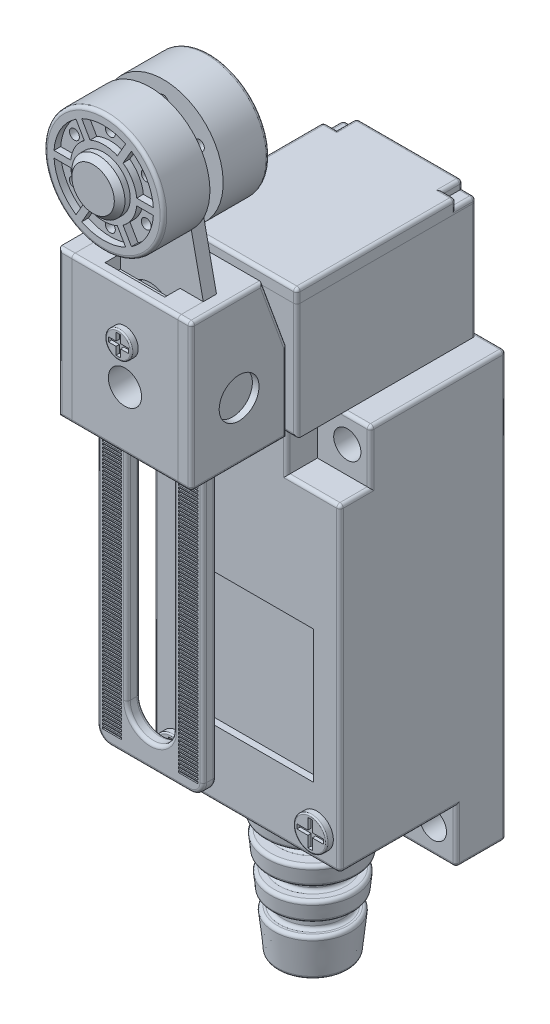
SolidWorks part; units mm, degrees
ref_plane "前视基准面" through (0, 0, 0) normal (0, 0, 1) x (1, 0, 0)
ref_plane "上视基准面" through (0, 0, 0) normal (0, 1, 0) x (1, 0, 0)
ref_plane "右视基准面" through (0, 0, 0) normal (1, 0, 0) x (0, 0, -1)
sketch "草图1" plane through (0, 0, 0) normal (0, 0, 1) x (1, 0, 0)
  line L0 (-30.7648, 0) -> (29.1625, 0) construction
  line L1 (0, 42.5) -> (0, 12.5) construction
  line L2 (-10, 24) -> (10, 24) construction
  line L3 (10, 24) -> (10, 4.5) construction
  line L4 (10, 4.5) -> (14, 4.5)
  line L5 (14, 4.5) -> (14, -59.5)
  line L6 (14, -59.5) -> (-14, -59.5)
  line L7 (-14, -59.5) -> (-14, 4.5)
  line L8 (-14, 4.5) -> (-10, 4.5)
  line L9 (-10, 4.5) -> (-10, 24) construction
  line L10 (-10, 4.5) -> (10, 4.5)
  line L11 (0, 0) -> (0, -73.5) construction
  line L12 (0, 0) -> (0, 12.5) construction
  line L13 (25, 42.5) -> (25, 12.5) construction
  line L14 (25, 12.5) -> (25, -37.5) construction
  line L15 (25, 42.5) -> (25, 48.5) construction
  arc A0 (11.2553, 40.3086) -> (-10.9644, 40.4246) centre (0, 12.5) ccw construction
  dimension "L" = 30
  dimension "D1" = 80
  dimension "A" = 28
  dimension "D2" = 6
  dimension "B2" = 64
  dimension "D3" = 20
  dimension "D4" = 25
  dimension "C" = 19.5
  dimension "B" = 12.5
  dimension "D6" = 4.5
  dimension "B1" = 14
extrude "凸台-拉伸1" add sketch "草图1" along normal mid plane 25
sketch "草图2" plane through (14, 0, 0) normal (1, 0, 0) x (0, 0, -1)
  line L0 (-12.5, -59.5) -> (-12.5, -51.5)
  line L1 (-12.5, -59.5) -> (5, -59.5)
  line L2 (-12.5, -51.5) -> (5, -51.5)
  line L3 (5, -59.5) -> (5, -51.5)
  line L4 (-12.5, -59.5) -> (-12.5, 4.5) construction
  line L5 (12.5, -59.5) -> (12.5, 4.5) construction
  dimension "F" = 7.5
  dimension "D2" = 8
extrude "切除-拉伸1" cut sketch "草图2" against normal through all
sketch "草图3" plane through (14, 0, 0) normal (1, 0, 0) x (0, 0, -1)
  line L0 (-12.5, 4.5) -> (-7.9, 4.5)
  line L1 (-12.5, 4.5) -> (-12.5, -3.5)
  line L2 (-7.9, 4.5) -> (-7.9, -3.5)
  line L3 (-12.5, -3.5) -> (-7.9, -3.5)
  line L4 (-12.5, 4.5) -> (12.5, 4.5) construction
  line L5 (12.5, -59.5) -> (12.5, 4.5) construction
  dimension "G" = 20.4
  dimension "D2" = 8
extrude "切除-拉伸2" cut sketch "草图3" against normal blind 8
mirror "镜向1" about plane through (0, 0, 0) normal (1, 0, 0) of "切除-拉伸2"
sketch "草图4" plane through (0, 0, 7.9) normal (0, 0, 1) x (1, 0, 0)
  line L0 (-10.5, 0.5314) -> (-10.5, -55.4686) construction
  line L2 (-6, 4.5) -> (-14, 4.5) construction
  line L3 (0, 0) -> (0, -19.4871) construction
  circle A0 centre (-10.5, 0.5314) radius 2.05
  circle A1 centre (-10.5, -55.4686) radius 2.05
  point P6 (-10, 4.5)
  dimension "D1" = 4.1
  dimension "I" = 4.1
  dimension "D4" = 4
  dimension "H" = 56
  dimension "A1" = 21
extrude "切除-拉伸3" cut sketch "草图4" against normal through all
mirror "镜向2" about plane through (0, 0, 0) normal (1, 0, 0) of "切除-拉伸3"
sketch "草图5" plane through (0, -51.5, 0) normal (0, -1, 0) x (1, 0, 0)
  line L0 (-14, -12.5) -> (14, -12.5) construction
  line L1 (0, -2.067) -> (0, 4.1058) construction
  circle A0 centre (0, 2.6) radius 7.55
  dimension "D1" = 15.1
  dimension "D2" = 15.1
extrude "凸台-拉伸3" add sketch "草图5" along normal up to vertex (22 mm away) draft 6 up to point (0, -73.5, 0)
ref_plane "基准面1" through (0, 0, 2.6) normal (0, 0, -1) x (-1, 0, 0)
sketch "草图6" plane through (0, 0, 2.6) normal (0, 0, -1) x (-1, 0, 0)
  line L0 (0, -51.5) -> (0, -73.5) construction
  line L1 (-7.55, -51.5) -> (7.55, -51.5) construction
  line L2 (-5.2377, -73.5) -> (5.2377, -73.5) construction
  line L3 (-4.5, -55.5) -> (-7.5, -55.5)
  line L4 (-4.5, -55.5) -> (-4.5, -57.5)
  line L5 (-7.5, -55.5) -> (-7.5, -57.5)
  line L6 (-4.5, -57.5) -> (-7.5, -57.5)
  line L9 (-4.5, -60.5) -> (-7.5, -60.5)
  line L10 (-4.5, -60.5) -> (-4.5, -62.5)
  line L11 (-7.5, -60.5) -> (-7.5, -62.5)
  line L13 (-4.5, -62.5) -> (-7.5, -62.5)
  line L15 (-4.5, -65.5) -> (-6.5, -65.5)
  line L16 (-4.5, -65.5) -> (-4.5, -67.5)
  line L18 (-6.5, -65.5) -> (-6.5, -67.5)
  line L19 (-4.5, -67.5) -> (-6.5, -67.5)
  line L21 (-4.5, -55.5) -> (-4.5, -51.5) construction
  line L22 (-4.5, -60.5) -> (-4.5, -57.5) construction
  line L23 (-4.5, -65.5) -> (-4.5, -62.5) construction
  dimension "D1" = 4
  dimension "D2" = 2
  dimension "D3" = 3
  dimension "D4" = 3
  dimension "D5" = 4.5
  dimension "D6" = 2
  dimension "D7" = 2
  dimension "D8" = 3
  dimension "D9" = 3
  dimension "D10" = 2
revolve "切除-旋转1" cut sketch "草图6" angle 360 about L0
sketch "草图7" plane through (0, 0, 12.5) normal (0, 0, 1) x (1, 0, 0)
  line L0 (0, 0) -> (0, -48.4796) construction
  line L1 (-14, -51.5) -> (14, -51.5) construction
  line L2 (6, 4.5) -> (-6, 4.5) construction
  circle A0 centre (-10.5, -47.5) radius 2.5
  circle A1 centre (10.5, -47.5) radius 2.5
  circle A2 centre (0, 0.5) radius 2.5
  dimension "M3" = 5
  dimension "D2" = 21
  dimension "D3" = 4
  dimension "D4" = 4
extrude "凸台-拉伸4" add sketch "草图7" along normal blind 1
sketch "草图8" plane through (0, 0, 13.5) normal (0, 0, 1) x (1, 0, 0)
  line L0 (-14, -47.5) -> (-7.3529, -47.5) construction
  line L1 (-14, -3.5) -> (-14, -51.5) construction
  line L2 (-10.5, -50.6113) -> (-10.5, -43.7188) construction
  line L3 (7.0475, -47.5) -> (13.5803, -47.5) construction
  line L4 (10.5, -50.6113) -> (10.5, -43.7188) construction
  line L5 (-3.5148, 0.5) -> (3.3232, 0.5) construction
  line L6 (0, -2.9168) -> (0, 3.9916) construction
  line L7 (-2, 0.84) -> (-2, 0.16)
  line L8 (-2, 0.84) -> (-0.325, 0.84)
  line L9 (-2, 0.16) -> (-0.325, 0.16)
  line L10 (2, 0.84) -> (2, 0.16)
  line L11 (-0.325, -1.5) -> (0.325, -1.5)
  line L12 (-0.325, -1.5) -> (-0.325, 0.16)
  line L13 (0.325, -1.5) -> (0.325, 0.16)
  line L14 (-0.325, 2.5) -> (0.325, 2.5)
  line L15 (-12.5, -47.16) -> (-12.5, -47.84)
  line L16 (-12.5, -47.16) -> (-10.84, -47.16)
  line L17 (-12.5, -47.84) -> (-10.84, -47.84)
  line L18 (-8.5, -47.16) -> (-8.5, -47.84)
  line L19 (-10.84, -49.5) -> (-10.16, -49.5)
  line L20 (-10.84, -49.5) -> (-10.84, -47.84)
  line L21 (-10.16, -49.5) -> (-10.16, -47.84)
  line L22 (-10.84, -45.5) -> (-10.16, -45.5)
  line L23 (-10.16, -47.16) -> (-8.5, -47.16)
  line L24 (-10.84, -47.16) -> (-10.84, -45.5)
  line L25 (-10.16, -47.16) -> (-10.16, -45.5)
  line L26 (-10.16, -47.84) -> (-8.5, -47.84)
  line L27 (0.325, 0.84) -> (2, 0.84)
  line L28 (-0.325, 0.84) -> (-0.325, 2.5)
  line L29 (0.325, 0.16) -> (2, 0.16)
  line L30 (0.325, 0.84) -> (0.325, 2.5)
  line L31 (10.84, -47.84) -> (12.5, -47.84)
  line L32 (8.5, -47.16) -> (10.16, -47.16)
  line L33 (8.5, -47.16) -> (8.5, -47.84)
  line L34 (8.5, -47.84) -> (10.16, -47.84)
  line L35 (12.5, -47.16) -> (12.5, -47.84)
  line L36 (10.16, -45.5) -> (10.84, -45.5)
  line L37 (10.16, -45.5) -> (10.16, -47.16)
  line L38 (10.16, -49.5) -> (10.84, -49.5)
  line L39 (10.84, -45.5) -> (10.84, -47.16)
  line L40 (10.16, -47.84) -> (10.16, -49.5)
  line L41 (10.84, -47.16) -> (12.5, -47.16)
  line L42 (10.84, -47.84) -> (10.84, -49.5)
  dimension "D1" = 0.68
  dimension "D2" = 0.65
  dimension "D3" = 4
  dimension "D4" = 4
  dimension "D5" = 0.68
  dimension "D6" = 0.68
  dimension "D7" = 4
  dimension "D8" = 4
  dimension "D9" = 0.68
  dimension "D10" = 0.68
  dimension "D11" = 4
  dimension "D12" = 4
extrude "切除-拉伸4" cut sketch "草图8" against normal blind 0.5
fillet "圆角1" radius 0.5 29 edges at (0, 4.5, -12.5) (14, 4.5, -2.3) (10, 4.5, 7.9) (14, 0.5, 7.9) (14, -3.5, 10.2) (10, -3.5, 12.5) (6, 0.5, 12.5) (6, 4.5, 10.2) (-6, 4.5, 10.2) (0, 4.5, 12.5) (-14, 4.5, -2.3) (-10, 4.5, 7.9) (-14, 0.5, 7.9) (-6, 0.5, 12.5) (-10, -3.5, 12.5) (-14, -27.5, -12.5) (-14, -27.5, 12.5) (-14, -51.5, 3.75) (-14, -59.5, -8.75) (-14, -55.5, -5) (0, -59.5, -12.5) (0, -59.5, -5) (14, -27.5, -12.5) (14, -59.5, -8.75) (14, -55.5, -5) (14, -51.5, 3.75) (0, -51.5, 12.5) (14, -27.5, 12.5) (-14, -3.5, 10.2)
fillet "圆角3" radius 0.5 13 edges at (-7.1296, -55.5, 2.6) (6.9194, -57.5, 2.6) (-4.5, -55.5, 2.6) (-4.5, -57.5, 2.6) (-6.6041, -60.5, 2.6) (-4.5, -60.5, 2.6) (6.3939, -62.5, 2.6) (-4.5, -62.5, 2.6) (-6.0785, -65.5, 2.6) (-4.5, -65.5, 2.6) (-4.5, -67.5, 2.6) (5.8683, -67.5, 2.6) (5.2377, -73.5, 2.6)
sketch "草图9" plane through (0, 0, 12.5) normal (0, 0, 1) x (1, 0, 0)
  line L0 (-14, -51) -> (-14, -4) construction
  line L1 (-10, -21.5) -> (10, -21.5)
  line L2 (-10, -21.5) -> (-10, -41.5)
  line L3 (-10, -41.5) -> (10, -41.5)
  line L4 (10, -21.5) -> (10, -41.5)
  line L5 (-7.55, -51.5) -> (7.55, -51.5) construction
  dimension "D1" = 20
  dimension "D2" = 4
  dimension "D3" = 20
  dimension "D4" = 10
extrude "切除-拉伸5" cut sketch "草图9" against normal blind 1
sketch "草图10" plane through (0, 0, 0) normal (1, 0, 0) x (0, 0, -1)
  line L0 (12, 14.25) -> (-34.4, 14.25) construction
  line L1 (12, 4.5) -> (-15, 4.5)
  line L2 (12, 4.5) -> (12, 24)
  line L3 (12, 24) -> (-15, 24)
  line L4 (-15, 4.5) -> (-15, 24)
  line L5 (-16.5, 5.5) -> (-30.9, 5.5)
  line L6 (-30.9, 5.5) -> (-30.9, 27.5)
  line L7 (-30.9, 27.5) -> (-20.1397, 27.5)
  line L8 (12, 54) -> (-35.7, 54) construction
  line L9 (-20.1397, 27.5) -> (-16.5, 17.5)
  line L10 (12, 24) -> (12, 54) construction
  line L11 (-16.5, 17.5) -> (-16.5, 5.5)
  line L12 (12, 50) -> (-21.5, 50) construction
  line L13 (12, 48) -> (-30.7, 48) construction
  line L14 (12, 52) -> (-16.5, 52) construction
  line L16 (2, 4.5) -> (2, 7.4237) construction
  line L17 (12.5, 4) -> (12.5, -59) construction
  dimension "D12" = 2
  dimension "J" = 19.5
  dimension "D2" = 27
  dimension "D3" = 3.5
  dimension "K" = 46.4
  dimension "D4" = 1
  dimension "D5" = 1.5
  dimension "D6" = 22
  dimension "D7" = 10
  dimension "D8" = 20
  dimension "D11" = 2
  dimension "D17" = 2
  dimension "C3" = 47.7
  dimension "D18" = 30
  dimension "N" = 28.5
  dimension "O" = 10.5
  dimension "C2" = 33.5
  dimension "C1" = 42.7
extrude "凸台-拉伸5" add sketch "草图10" along normal mid plane 20
sketch "草图11" plane through (0, 0, 30.9) normal (0, 0, 1) x (1, 0, 0)
  circle A0 centre (0, 14.25) radius 3
  dimension "D1" = 6
extrude "凸台-拉伸6" add sketch "草图11" against normal up to surface (15.9 mm away) up to face at (0, 14.25, 15)
sketch "草图12" plane through (0, 5.5, 0) normal (0, -1, 0) x (1, 0, 0)
  line L0 (0, 30.9) -> (0, 19.6877) construction
  line L1 (-8, 27.1) -> (8, 27.1)
  line L2 (-8, 27.1) -> (-8, 25.1)
  line L3 (-8, 25.1) -> (8, 25.1)
  line L4 (8, 27.1) -> (8, 25.1)
  line L5 (10, 30.9) -> (-10, 30.9) construction
  line L6 (0, -12) -> (0, 21.5) construction
  dimension "D1" = 2
  dimension "D2" = 3.8
  dimension "D3" = 16
extrude "凸台-拉伸7" add sketch "草图12" along normal up to vertex (-43 mm away) and the other way up to vertex (-43 mm away) up to point (25, 48.5, 0) other way up to point (25, -37.5, 0)
sketch "草图13" plane through (0, 0, 27.1) normal (0, 0, 1) x (1, 0, 0)
  line L0 (0, -33.4812) -> (0, 45.9522) construction
  line L1 (0, 22.5) -> (0, -30.5) construction
  line L2 (3.5, 22.5) -> (3.5, -30.5)
  line L3 (-3.5, 22.5) -> (-3.5, -30.5)
  line L4 (8, -37.5) -> (-8, -37.5) construction
  line L5 (-8, 27.5) -> (-4.5283, 43.8331)
  line L6 (8, 27.5) -> (4.5283, 43.8331)
  line L7 (-8, 27.5) -> (-8, 48.5)
  line L8 (-8, 48.5) -> (8, 48.5)
  line L9 (8, 48.5) -> (8, 27.5)
  line L10 (8, 27.5) -> (-8, 27.5) construction
  line L11 (0, 47.5) -> (2.6556, 47.5) construction
  arc A0 (3.5, 22.5) -> (-3.5, 22.5) centre (0, 22.5) ccw
  arc A1 (-3.5, -30.5) -> (3.5, -30.5) centre (0, -30.5) ccw
  arc A2 (-4.5283, 43.8331) -> (4.5283, 43.8331) centre (0, 42.8705) cw
  point P5 (0, -4)
  dimension "D4" = 1
  dimension "D1" = 7
  dimension "D2" = 7
  dimension "D3" = 53
  dimension "D5" = 78
extrude "切除-拉伸6" cut sketch "草图13" against normal up to surface (2 mm away) up to face at (0, 38, 25.1)
sketch "草图14" plane through (0, 5.5, 0) normal (0, -1, 0) x (1, 0, 0)
  line L0 (-8, 27.1) -> (-8, 30.9)
  line L1 (10, 30.9) -> (-10, 30.9) construction
  line L2 (8, 27.1) -> (8, 30.9)
split line "分割线1"
sketch "草图15" plane through (0, 0, 30.9) normal (0, 0, 1) x (1, 0, 0)
  line L0 (-8, 5.5) -> (-8, 27.5)
  line L1 (8, 27.5) -> (8, 5.5)
split line "分割线2"
sketch "草图16" plane through (0, 5.5, 0) normal (0, -1, 0) x (1, 0, 0)
  line L0 (8, 27.1) -> (8, 30.9) construction
  line L1 (-4.5, 29.4) -> (4.5, 29.4)
  line L2 (-4.5, 29.4) -> (-4.5, 27.1)
  line L3 (-4.5, 27.1) -> (4.5, 27.1)
  line L4 (4.5, 29.4) -> (4.5, 27.1)
  line L5 (-8, 27.1) -> (-8, 30.9) construction
  line L6 (8, 30.9) -> (-8, 30.9) construction
  line L7 (8, 27.1) -> (-8, 27.1) construction
  dimension "D1" = 3.5
  dimension "D2" = 3.5
  dimension "D3" = 1.5
extrude "切除-拉伸7" cut sketch "草图16" against normal blind 2
ref_plane "基准面2" through (0, 16.5, 0) normal (0, 1, 0) x (-1, 0, 0)
sketch "草图17" plane through (0, 0, 27.1) normal (0, 0, 1) x (1, 0, 0)
  circle A0 centre (0, 42.5) radius 9
  dimension "P" = 18
extrude "凸台-拉伸8" add sketch "草图17" along normal blind 7
mirror "镜向4" about plane through (0, 16.5, 0) normal (0, 1, 0) of "切除-拉伸7"
sketch "草图18" plane through (0, 0, 34.1) normal (0, 0, 1) x (1, 0, 0)
  circle A0 centre (0, 42.5) radius 7.5
  circle A1 centre (0, 42.5) radius 5
  dimension "D1" = 15
  dimension "D2" = 10
extrude "切除-拉伸8" cut sketch "草图18" against normal blind 1
sketch "草图19" plane through (0, 0, 33.1) normal (0, 0, 1) x (1, 0, 0)
  line L0 (0, 47.5) -> (0, 50) construction
  circle A0 centre (0, 42.5) radius 5 construction
  circle A1 centre (0, 42.5) radius 5 construction
  circle A2 centre (0, 42.5) radius 7.5 construction
  circle A3 centre (0, 48.75) radius 0.75
  dimension "D1" = 1.5
extrude "切除-拉伸11" cut sketch "草图19" against normal up to surface (6 mm away) up to face at (0, 44.702, 27.1)
sketch "草图20" plane through (0, 0, 33.1) normal (0, 0, 1) x (1, 0, 0)
  line L0 (-10.0844, 42.5) -> (9.682, 42.5) construction
  line L1 (0, 42.5) -> (0, 12.5) construction
  line L2 (4.5, 43) -> (8, 43)
  line L3 (4.5, 43) -> (4.5, 42)
  line L4 (4.5, 42) -> (8, 42)
  line L5 (8, 43) -> (8, 42)
  dimension "D1" = 1
  dimension "D2" = 4.5
  dimension "D3" = 3.5
extrude "凸台-拉伸9" add sketch "草图20" along normal blind 1
pattern_circular "阵列(圆周)1" count 6 every 60 about axis through (0, 42.5, 34.1) along (0, 0, 1) of "凸台-拉伸9", "切除-拉伸11"
ref_plane "基准面3" through (0, 0, 26.1) normal (0, 0, -1) x (-1, 0, 0)
mirror "镜向6" about plane through (0, 0, 26.1) normal (0, 0, -1) of "切除-拉伸8", "凸台-拉伸8"
sketch "草图26" plane through (0, 0, 19.1) normal (0, 0, -1) x (-1, 0, 0)
  line L0 (0, 47.5) -> (0, 50) construction
  circle A0 centre (0, 42.5) radius 5 construction
  circle A1 centre (0, 42.5) radius 5 construction
  circle A2 centre (0, 42.5) radius 7.5 construction
  circle A3 centre (0, 48.75) radius 0.75
  dimension "D1" = 1.5
extrude "切除-拉伸15" cut sketch "草图26" against normal up to surface (6 mm away) up to face at (0, 44.702, 25.1)
sketch "草图27" plane through (0, 0, 19.1) normal (0, 0, -1) x (-1, 0, 0)
  line L0 (-9.6322, 42.5) -> (9.676, 42.5) construction
  line L2 (4.5, 43) -> (8, 43)
  line L3 (4.5, 43) -> (4.5, 42)
  line L4 (4.5, 42) -> (8, 42)
  line L5 (8, 43) -> (8, 42)
  circle A0 centre (0, 42.5) radius 5 construction
  dimension "D1" = 1
  dimension "D2" = 3.5
  dimension "D3" = 4.5
extrude "凸台-拉伸12" add sketch "草图27" along normal up to surface (1 mm away) up to face at (9, 42.5, 18.1)
pattern_circular "阵列(圆周)3" count 6 every 60 about axis through (0, 42.5, 18.1) along (0, 0, 1) of "凸台-拉伸12", "切除-拉伸15"
sketch "草图21" plane through (0, 0, 34.1) normal (0, 0, 1) x (1, 0, 0)
  circle A0 centre (0, 42.5) radius 4
  dimension "D1" = 8
extrude "凸台-拉伸10" add sketch "草图21" along normal up to vertex (1.6 mm away) and the other way up to vertex (17.6 mm away) up to point (0, 54, 35.7) other way up to point (0, 52, 16.5)
sketch "草图22" plane through (0, 0, 30.9) normal (0, 0, 1) x (1, 0, 0)
  circle A0 centre (0, 14.25) radius 2.5
  dimension "D1" = 5
extrude "切除-拉伸12" cut sketch "草图22" against normal up to surface (3.8 mm away) up to face at (0, -7.2917, 27.1)
sketch "草图23" plane through (0, 0, 30.9) normal (0, 0, 1) x (1, 0, 0)
  line L0 (0, 27.5) -> (0, 17.5) construction
  circle A0 centre (0, 20.25) radius 2
  circle A1 centre (0, 14.25) radius 2.5 construction
  dimension "M4" = 4
  dimension "D2" = 6
extrude "凸台-拉伸11" add sketch "草图23" along normal blind 1
sketch "草图24" plane through (0, 0, 31.9) normal (0, 0, 1) x (1, 0, 0)
  line L0 (-2.8059, 20.25) -> (2.5571, 20.25) construction
  line L1 (0, 17.5) -> (0, 23.3979) construction
  line L2 (0, 27.5) -> (0, 17.5) construction
  line L3 (0, 17.5) -> (0, 5.5) construction
  line L4 (0.34, 20.59) -> (1.5, 20.59)
  line L5 (-1.5, 20.59) -> (-0.34, 20.59)
  line L6 (-1.5, 20.59) -> (-1.5, 19.91)
  line L7 (-1.5, 19.91) -> (-0.34, 19.91)
  line L8 (1.5, 20.59) -> (1.5, 19.91)
  line L9 (-0.34, 21.75) -> (0.34, 21.75)
  line L10 (-0.34, 21.75) -> (-0.34, 20.59)
  line L11 (-0.34, 18.75) -> (0.34, 18.75)
  line L12 (0.34, 21.75) -> (0.34, 20.59)
  line L13 (-0.34, 19.91) -> (-0.34, 18.75)
  line L14 (0.34, 19.91) -> (1.5, 19.91)
  line L15 (0.34, 19.91) -> (0.34, 18.75)
  dimension "D1" = 0.68
  dimension "D2" = 0.68
  dimension "D3" = 3
  dimension "D4" = 3
extrude "切除-拉伸13" cut sketch "草图24" against normal blind 0.5
sketch "草图25" plane through (10, 0, 0) normal (1, 0, 0) x (0, 0, -1)
  line L0 (-23.7, 14.25) -> (-15, 14.25) construction
  line L1 (-15, 17.25) -> (-15, 11.25) construction
  line L2 (-23.7, 5.5) -> (-23.7, 18.9404) construction
  line L3 (-30.9, 5.5) -> (-16.5, 5.5) construction
  circle A0 centre (-23.7, 14.25) radius 3
  dimension "M6" = 6
extrude "切除-拉伸14" cut sketch "草图25" against normal blind 1
cosmetic thread "装饰螺纹线1" parameters "D2"=6
sketch "草图28" plane through (10, 0, 0) normal (1, 0, 0) x (0, 0, -1)
  line L0 (-15, 22) -> (12, 22)
  line L1 (-15, 24) -> (-15, 4.5) construction
  line L2 (12, 4.5) -> (12, 24) construction
  line L3 (12, 24) -> (-15, 24) construction
  dimension "D1" = 2
split line "分割线3"
sketch "草图29" plane through (0, 0, -12) normal (0, 0, -1) x (-1, 0, 0)
  line L0 (-10, 22) -> (10, 22)
split line "分割线4"
sketch "草图30" plane through (10, 0, 0) normal (1, 0, 0) x (0, 0, -1)
  line L1 (12, 24) -> (9, 24)
  line L2 (12, 24) -> (12, 22.75)
  line L3 (12, 22.75) -> (9, 22.75)
  line L4 (9, 24) -> (9, 22.75)
  dimension "D1" = 1.25
  dimension "D2" = 3
extrude "切除-拉伸16" cut sketch "草图30" against normal blind 2
mirror "镜向7" about plane through (0, 0, 0) normal (1, 0, 0) of "切除-拉伸16"
fillet "圆角5" radius 0.5 58 edges at (-3.5, -12.5, 25.1) (0, -34, 25.1) (0, -34, 27.1) (9, 5.5, 30.9) (9, 27.5, 30.9) (-9, 27.5, 30.9) (0, 27.5, 30.9) (-10, 22.5, 18.3199) (-10, 11.5, 16.5) (8, -16, 25.1) (3.5, -12.5, 25.1) (0, -37.5, 25.1) (0, -37.5, 27.1) (3.5, -11.5, 27.1) (-3.5, -11.5, 27.1) (-8, -16, 25.1) (-8, -16, 27.1) (4.5, 5.5, 28.25) (-4.5, 5.5, 28.25) (0, 5.5, 29.4) (4.5, 6.5, 29.4) (-4.5, 6.5, 29.4) (-10, 16.5, 30.9) (0, 5.5, 30.9) (-9, 5.5, 30.9) (10, 16.5, 30.9) (10, 27.5, 25.5199) (10, 22.5, 18.3199) (10, 11.5, 16.5) (10, 5.5, 23.7) (0, 4.5, 15) (-10, 23, 15) (-10, 13.25, 15) (-10, 24, 3) (-8, 24, -10.5) (-9, 24, -9) (-10, 23.375, -9) (-10, 22.75, -10.5) (-9, 22.75, -12) (-8, 23.375, -12) (-10, 13.25, -12) (-10, 22.375, -12) (0, 24, -12) (9, 22.75, -12) (8, 23.375, -12) (8, 24, -10.5) (9, 24, -9) (10, 23.375, -9) (10, 22.75, -10.5) (10, 22.375, -12) (10, 13.25, -12) (10, 24, 3) (10, 23, 15) (10, 13.25, 15) (8, -16, 27.1) (9, 42.5, 18.1) (9, 42.5, 34.1) (0, 24, 15)
fillet "圆角6" radius 2 6 edges at (7.8536, -37.3536, 26.9536) (7.8536, -37.3536, 25.2464) (-7.8536, -37.3536, 25.2464) (-7.8536, -37.3536, 26.9536) (-8, -37.5, 26.1) (8, -37.5, 26.1)
fillet "圆角7" radius 0.2 4 edges at (-8, -47.5, 13.5) (13, -47.5, 13.5) (2.5, 0.5, 13.5) (2, 20.25, 31.9)
chamfer "倒角1" distance 0.8 angle 45 2 edges at (4, 42.5, 16.5) (4, 42.5, 35.7)
sketch "草图31" plane through (0, 0, 27.1) normal (0, 0, 1) x (1, 0, 0)
  line L0 (-4.3, 5) -> (4.3, 5) construction
  line L1 (4.3, 5) -> (7.2, 5)
  line L2 (4.3, 5) -> (4.3, 4.7)
  line L3 (4.3, 4.7) -> (7.2, 4.7)
  line L4 (7.2, 5) -> (7.2, 4.7)
  line L5 (-7.2, 5) -> (-4.3, 5)
  line L6 (-7.2, 5) -> (-7.2, 4.7)
  line L7 (-7.2, 4.7) -> (-4.3, 4.7)
  line L8 (-4.3, 5) -> (-4.3, 4.7)
  line L9 (-7.5, 5.5) -> (-7.5, -35.5) construction
  line L10 (-4, -30.5) -> (-4, 7.5) construction
  line L11 (7.5, -35.5) -> (7.5, 5.5) construction
  line L12 (6, -37.5) -> (-6, -37.5) construction
  dimension "D1" = 0.3
  dimension "D2" = 0.3
  dimension "D3" = 0.3
  dimension "D4" = 42.5
  dimension "D5" = 0.3
extrude "切除-拉伸17" cut sketch "草图31" against normal blind 0.2
pattern_linear "阵列(线性)1" count 82 spacing 0.5 along (0, -1, 0) of "切除-拉伸17"
sketch "草图32" plane through (0, 5.5, 0) normal (0, -1, 0) x (1, 0, 0)
  line L0 (-8, 30.4) -> (-8, 26.6)
  line L1 (8, 30.4) -> (8, 26.6)
  arc A0 (-7.5, 27.1) -> (-8, 26.6) centre (-7.5, 26.6) ccw construction
split line "分割线5"
